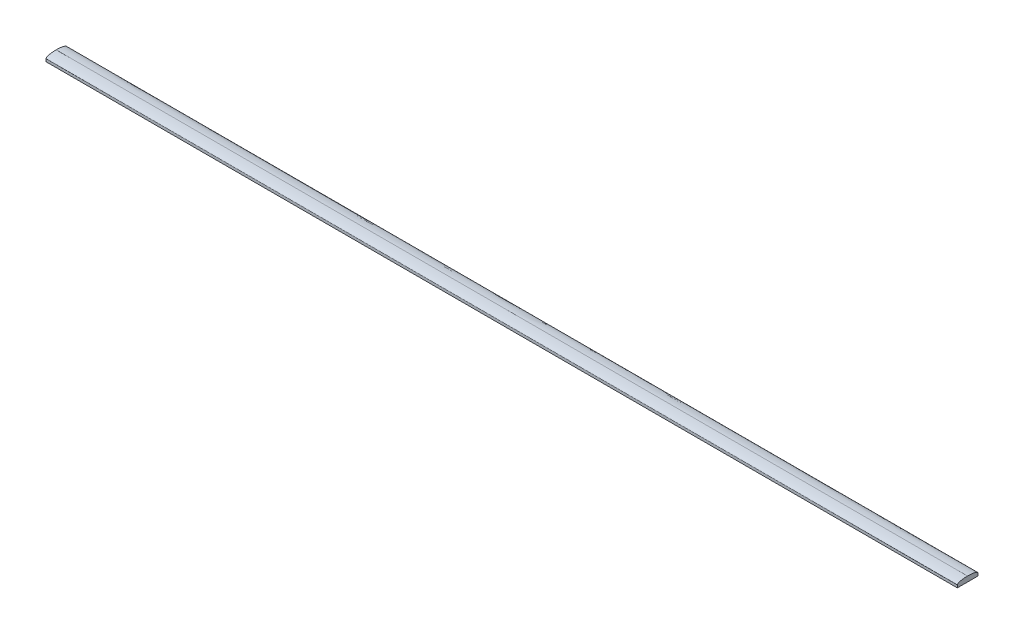
SolidWorks part; units mm, degrees
ref_plane "Front Plane" through (0, 0, 0) normal (0, 0, 1) x (1, 0, 0)
ref_plane "Top Plane" through (0, 0, 0) normal (0, 1, 0) x (1, 0, 0)
ref_plane "Right Plane" through (0, 0, 0) normal (1, 0, 0) x (0, 0, -1)
sketch "Sketch1" plane through (0, 0, 0) normal (0, 1, 0) x (1, 0, 0)
  line L1 (0, 0) -> (441.198, 0)
  line L2 (0, 0) -> (0, 10)
  line L3 (0, 10) -> (441.198, 10)
  line L4 (441.198, 0) -> (441.198, 10)
  dimension "D1" = 10
  dimension "Strip Length" = 441.198
extrude "Boss-Extrude1" add sketch "Sketch1" along normal blind 2.54
fillet "Fillet5" radius 1.27 2 edges at (220.599, 2.54, -10) (220.599, 2.54, 0) second distance 5.08 first distance on face at (220.599, 1.27, -10) first distance on face at (220.599, 1.27, 0)
